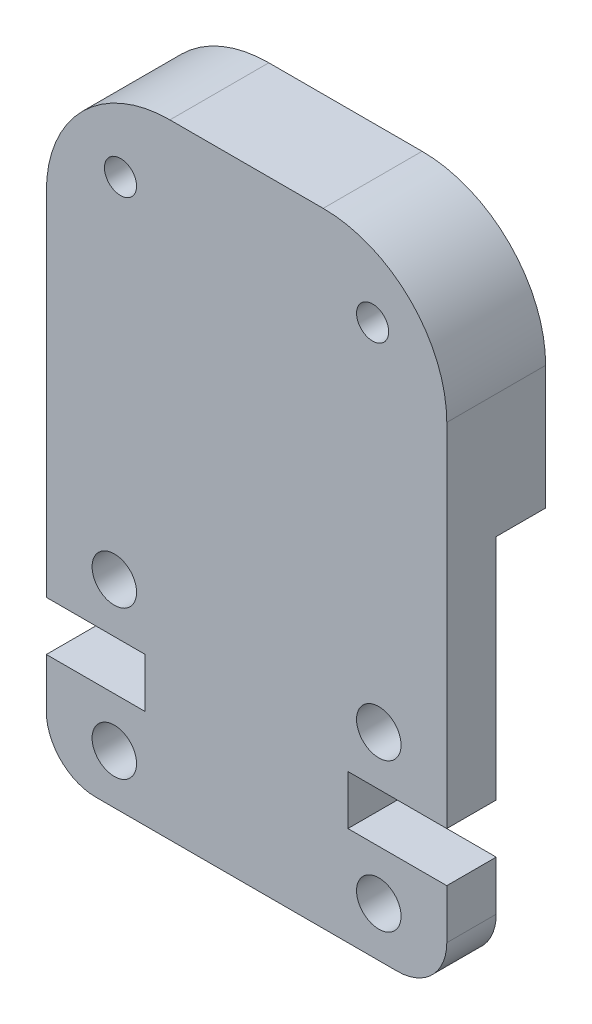
SolidWorks part; units mm, degrees
ref_plane "Front Plane" through (0, 0, 0) normal (0, 0, 1) x (1, 0, 0)
ref_plane "Top Plane" through (0, 0, 0) normal (0, 1, 0) x (1, 0, 0)
ref_plane "Right Plane" through (0, 0, 0) normal (1, 0, 0) x (0, 0, -1)
sketch "Sketch1" plane through (0, 0, 0) normal (0, 0, 1) x (1, 0, 0)
  line L0 (8.1, 25.23) -> (8.1, 0) construction
  line L1 (2, 0) -> (14.2, 0)
  line L2 (5, 25.23) -> (11.2, 25.23)
  line L3 (12.2, 4) -> (16.2, 4)
  line L4 (12.2, 6) -> (12.2, 4)
  line L5 (16.2, 6) -> (12.2, 6)
  line L6 (16.2, 2) -> (16.2, 4)
  line L7 (16.2, 20.23) -> (16.2, 6)
  line L22 (0, 20.23) -> (0, 6)
  line L33 (0, 2) -> (0, 4)
  line L34 (0, 6) -> (4, 6)
  line L36 (4, 6) -> (4, 4)
  line L37 (4, 4) -> (0, 4)
  circle A0 centre (13.45, 2) radius 0.9
  arc A1 (16.2, 2) -> (14.2, 0) centre (14.2, 2) cw
  circle A2 centre (13.2, 22.23) radius 0.65
  arc A3 (11.2, 25.23) -> (16.2, 20.23) centre (11.2, 20.23) cw
  circle A4 centre (2.75, 8) radius 0.9
  circle A5 centre (13.45, 8) radius 0.9
  arc A17 (5, 25.23) -> (0, 20.23) centre (5, 20.23) ccw
  circle A19 centre (3, 22.23) radius 0.65
  arc A21 (0, 2) -> (2, 0) centre (2, 2) ccw
  circle A23 centre (2.75, 2) radius 0.9
  dimension "D1" = 1.3
  dimension "D3" = 5
  dimension "D4" = 2
  dimension "D10" = 1.8
  dimension "D11" = 1.8
  dimension "D14" = 1.8
  dimension "D15" = 1.8
  dimension "D5" = 3
  dimension "D7" = 8.1
  dimension "D13" = 25.23
  dimension "D12" = 3
  dimension "D2" = 6
  dimension "D6" = 2.75
  dimension "D8" = 2.75
  dimension "D9" = 4
extrude "Boss-Extrude1" add sketch "Sketch1" along normal blind 4
sketch "Sketch2" plane through (0, 0, 0) normal (0, 0, 1) x (1, 0, 0)
  line L0 (0, 0) -> (16.2, 0)
  line L1 (16.2, 0) -> (16.2, 15.23)
  line L2 (16.2, 15.23) -> (0, 15.23)
  line L3 (0, 15.23) -> (0, 0)
  dimension "D1" = 15.23
extrude "Cut-Extrude1" cut sketch "Sketch2" along normal blind 2
equation "\"D7@Sketch1\"= \"fingerWidth@parametersSketch@prostheticParameters.SLDPRT\" / 2 'DIP width"
equation "\"D13@Sketch1\"= \"HL@parametersSketch@prostheticParameters.SLDPRT\" * 0.158 - 4 'DIP length - Sil. Sht DIP"
equation "\"D1@Sketch2\"= \"HL@parametersSketch@prostheticParameters.SLDPRT\" * 0.158 - 4 - 10 'DIP Cut fingertip"
equation "\"D1@Sketch1\"= 1 + \"tol1@parametersSketch@prostheticParameters.SLDPRT\""
equation "\"D10@Sketch1\"= 1.5 + \"tol1@parametersSketch@prostheticParameters.SLDPRT\""
equation "\"D11@Sketch1\"= 1.5 + \"tol1@parametersSketch@prostheticParameters.SLDPRT\""
equation "\"D14@Sketch1\"= 1.5 + \"tol1@parametersSketch@prostheticParameters.SLDPRT\""
equation "\"D15@Sketch1\"= 1.5 + \"tol1@parametersSketch@prostheticParameters.SLDPRT\""
